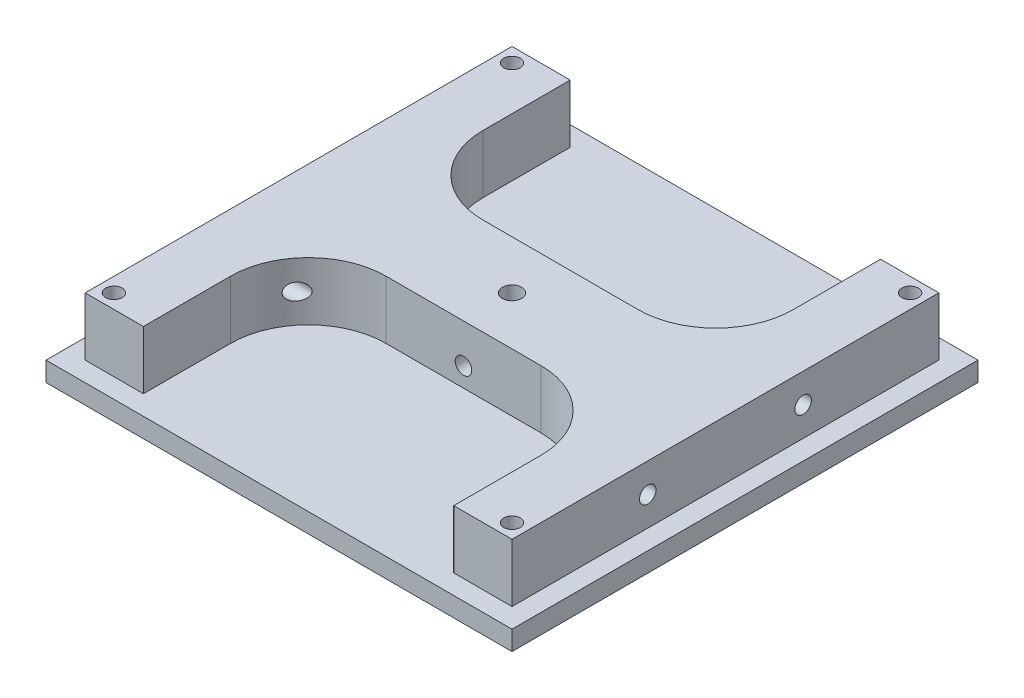
SolidWorks part; units mm, degrees
material "6061-T6 (SS)"
ref_plane "Front Plane" through (0, 0, 0) normal (0, 0, 1) x (1, 0, 0)
ref_plane "Top Plane" through (0, 0, 0) normal (0, 1, 0) x (1, 0, 0)
ref_plane "Right Plane" through (0, 0, 0) normal (1, 0, 0) x (0, 0, -1)
sketch "Sketch1" plane through (0, 0, 0) normal (0, 1, 0) x (1, 0, 0)
  line L1 (-38.1, -38.1) -> (38.1, -38.1)
  line L2 (-38.1, -38.1) -> (-38.1, 38.1)
  line L3 (-38.1, 38.1) -> (38.1, 38.1)
  line L4 (38.1, -38.1) -> (38.1, 38.1)
  line L5 (-38.1, -38.1) -> (38.1, 38.1) construction
  line L6 (-38.1, 38.1) -> (38.1, -38.1) construction
  point P0 (0, 0)
  dimension "D1" = 76.2
  dimension "D2" = 76.2
extrude "Boss-Extrude1" add sketch "Sketch1" along normal blind 3.175
sketch "Sketch2" plane through (0, 3.175, 0) normal (0, 1, 0) x (1, 0, 0)
  line L0 (-38.1, 38.1) -> (-38.1, -38.1) construction
  line L1 (34.8971, -34.8971) -> (-34.8971, -34.8971)
  line L2 (34.8971, -34.8971) -> (34.8971, 34.8971)
  line L3 (34.8971, 34.8971) -> (-34.8971, 34.8971)
  line L4 (-34.8971, -34.8971) -> (-34.8971, 34.8971)
  line L5 (38.1, -38.1) -> (38.1, 38.1) construction
  line L6 (-38.1, -38.1) -> (38.1, -38.1) construction
  line L14 (38.1, 38.1) -> (-38.1, 38.1) construction
  point P0 (0, 0)
  point P6 (0, 0)
  dimension "D1" = 3.2029
  dimension "D2" = 3.2029
  dimension "D3" = 3.2029
  dimension "D4" = 3.2029
extrude "Boss-Extrude2" add sketch "Sketch2" along normal blind 9.525
sketch "Sketch8" plane through (34.8971, 0, 0) normal (1, 0, 0) x (0, 0, -1)
  line L0 (-38.1, 3.175) -> (38.1, 3.175) construction
  point P0 (-12.7, 7.9375)
  dimension "D1" = 4.7625
  dimension "D2" = 12.7
hole_wizard "#6-32 Tapped Hole3" positions "Sketch10" profile "Sketch9" tap size "#6-32" standard "ANSI Inch"
sketch "Sketch10" plane through (34.8971, 0, 0) normal (1, 0, 0) x (0, 0, -1)
  point P0 (-12.7, 7.9375)
sketch "Sketch9" plane through (34.8971, 7.9375, 12.7) normal (0, 1, 0) x (0, 0, -1)
  line L0 (0, 0) -> (0, 11.9887)
  line L1 (0, 11.9887) -> (1.3525, 11.176)
  line L2 (1.3525, 11.176) -> (1.3525, 0)
  line L5 (1.3525, 0) -> (0, 0)
  line L10 (0, 11.9887) -> (-1.3526, 11.176) construction
  line L11 (0, -6.35) -> (0, 107.95) construction
  dimension "Tap Drill Dia." = 2.7051
  dimension "Tap Drill Depth" = 11.176
  dimension "Drill Angle" = 118
cosmetic thread "Hole Thread1" parameters "D1"=7.112, "D2"=3.5052
mirror "Mirror1" about plane through (0, 0, 0) normal (0, 0, 1) of "#6-32 Tapped Hole3"
mirror "Mirror2" about plane through (0, 0, 0) normal (1, 0, 0) of "Mirror1"
sketch "Sketch11" plane through (0, 0, 0) normal (0, -1, 0) x (1, 0, 0)
  circle A0 centre (32.5501, -32.5501) radius 2.032
  dimension "D1" = 4.064
hole_wizard "#6-32 Tapped Hole1" positions "Sketch13" profile "Sketch12" tap size "#6-32" standard "ANSI Inch" end condition through all
sketch "Sketch13" plane through (0, 0, 0) normal (0, -1, 0) x (-1, 0, 0)
  point P0 (-32.5501, 32.5501)
sketch "Sketch12" plane through (32.5501, 0, -32.5501) normal (1, 0, 0) x (0, 0, -1)
  line L0 (0, 0) -> (0, 12.7)
  line L1 (0, 12.7) -> (1.3525, 12.7)
  line L2 (1.3525, 12.7) -> (1.3525, 0)
  line L5 (1.3525, 0) -> (0, 0)
  line L11 (0, -6.35) -> (0, 107.95) construction
  dimension "Thru Tap Drill Dia." = 2.7051
  dimension "Thru Tap Drill Depth" = 12.7
cosmetic thread "Hole Thread2" parameters "D2"=3.5052
ref_axis "Axis1" through (0, -0.635, 0) along (0, 1, 0)
pattern_circular "CirPattern1" count 4 over 360 about axis through (0, -0.635, 0) along (0, 1, 0) of "#6-32 Tapped Hole1"
sketch "Sketch14" plane through (0, 0, 0) normal (0, -1, 0) x (1, 0, 0)
  circle A0 centre (0, 0) radius 3.175
  dimension "D1" = 6.35
extrude "Cut-Extrude1" cut sketch "Sketch14" against normal through all
sketch "Sketch15" plane through (0, 12.7, 0) normal (0, 1, 0) x (1, 0, 0)
  line L0 (-25.3721, -7.9375) -> (25.3721, -7.9375)
  line L1 (25.3721, -7.9375) -> (25.3721, -34.8971)
  line L2 (-34.8971, -34.8971) -> (34.8971, -34.8971) construction
  line L3 (-25.3721, -7.9375) -> (-25.3721, -34.8971)
  line L4 (-34.8971, 34.8971) -> (-34.8971, -34.8971) construction
  line L5 (34.8971, -34.8971) -> (34.8971, 34.8971) construction
  line L6 (-25.3721, -34.8971) -> (25.3721, -34.8971)
  dimension "D1" = 9.525
  dimension "D2" = 9.525
  dimension "D3" = 7.9375
extrude "Cut-Extrude2" cut sketch "Sketch15" against normal blind 9.525
fillet "Fillet1" radius 12.7 2 edges at (25.3721, 7.9375, 7.9375) (-25.3721, 7.9375, 7.9375)
sketch "Sketch16" plane through (0, 0, 7.9375) normal (0, 0, 1) x (1, 0, 0)
  line L0 (12.6721, 3.175) -> (-12.6721, 3.175) construction
  point P0 (0, 6.35)
  dimension "D1" = 3.175
hole_wizard "#6-32 Tapped Hole2" positions "Sketch18" profile "Sketch17" tap size "#6-32" standard "ANSI Inch"
sketch "Sketch18" plane through (0, 0, 7.9375) normal (0, 0, 1) x (1, 0, 0)
  point P0 (0, 6.35)
sketch "Sketch17" plane through (0, 6.35, 7.9375) normal (1, 0, 0) x (0, -1, 0)
  line L0 (0, 0) -> (0, 10.4647)
  line L1 (0, 10.4647) -> (1.3525, 9.652)
  line L2 (1.3525, 9.652) -> (1.3525, 0)
  line L5 (1.3525, 0) -> (0, 0)
  line L10 (0, 10.4647) -> (-1.3526, 9.652) construction
  line L11 (0, -6.35) -> (0, 107.95) construction
  dimension "Tap Drill Dia." = 2.7051
  dimension "Tap Drill Depth" = 9.652
  dimension "Drill Angle" = 118
cosmetic thread "Hole Thread3" parameters "D1"=6.35, "D2"=3.5052
mirror "Mirror3" about plane through (0, 0, 0) normal (0, 0, 1) of "Cut-Extrude2", "Fillet1"
sketch "Sketch20" plane through (0, 12.7, 0) normal (0, 1, 0) x (1, 0, 0)
  circle A0 centre (0, 0) radius 1.5875
  circle M5 centre (0, 0) radius 3.175
  dimension "D1" = 3.175
extrude "Boss-Extrude3" add sketch "Sketch20" against normal blind 2.54 contours A0 M5 region at (-3.0852, 12.7, 0)
equation "\"D2@Sketch2\"=\"D1@Sketch2\""
equation "\"D2@Sketch1\"=\"D1@Sketch1\""
equation "\"D3@Sketch2\"=\"D2@Sketch2\""
equation "\"D4@Sketch2\"=\"D2@Sketch2\""
equation "\"D2@Sketch15\"=\"D1@Sketch15\""
